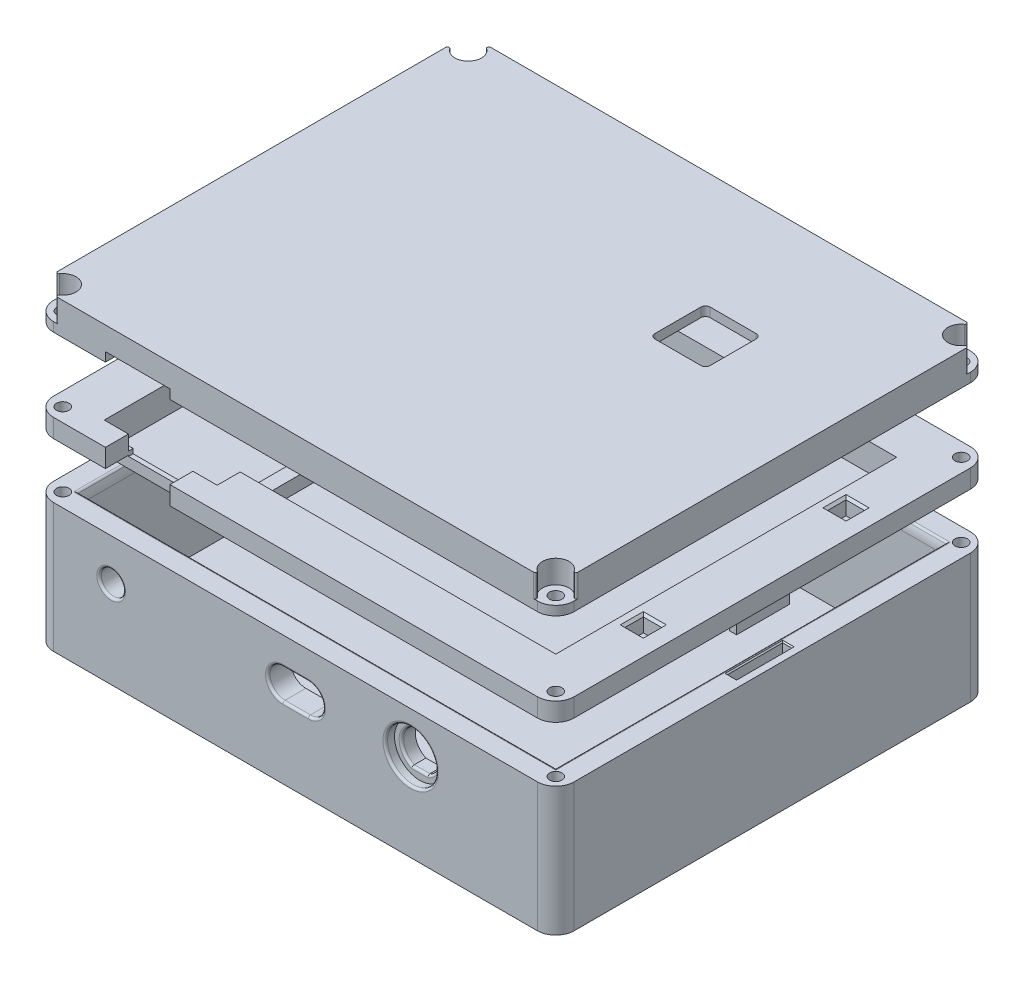
SolidWorks part; units mm, degrees
ref_plane "Front Plane" through (0, 0, 0) normal (0, 0, 1) x (1, 0, 0)
ref_plane "Top Plane" through (0, 0, 0) normal (0, 1, 0) x (1, 0, 0)
ref_plane "Right Plane" through (0, 0, 0) normal (1, 0, 0) x (0, 0, -1)
sketch "Sketch1" plane through (0, 0, 0) normal (0, 1, 0) x (1, 0, 0)
  line L0 (-1, 89) -> (104, 89)
  line L1 (0, 0) -> (103, 0)
  line L2 (0, 0) -> (0, 84)
  line L3 (0, 84) -> (103, 84)
  line L4 (103, 0) -> (103, 84)
  line L5 (108, -1) -> (108, 85)
  line L6 (-1, -5) -> (104, -5)
  line L7 (-5, -1) -> (-5, 85)
  line L8 (0, 0) -> (0, 13.5) construction
  line L9 (0, 84) -> (0, 72) construction
  line L10 (0, 0) -> (4, 0) construction
  line L11 (-5, 89) -> (108, 89) construction
  line L12 (108, -5) -> (108, 89) construction
  line L13 (-5, -5) -> (108, -5) construction
  line L14 (-5, -5) -> (-5, 89) construction
  line L15 (0, 13.5) -> (1.5, 13.5)
  line L20 (1.5, 13.5) -> (1.5, 0)
  line L21 (0, 72) -> (1.5, 72)
  line L22 (1.5, 72) -> (1.5, 84)
  line L23 (4, 0) -> (4, 1.5)
  line L24 (4, 1.5) -> (1.5, 1.5)
  arc A0 (104, 89) -> (108, 85) centre (104, 85) cw
  arc A1 (108, -1) -> (104, -5) centre (104, -1) cw
  arc A2 (-5, -1) -> (-1, -5) centre (-1, -1) ccw
  arc A3 (-5, 85) -> (-1, 89) centre (-1, 85) cw
  dimension "D7" = 4
  dimension "D1" = 103
  dimension "D2" = 84
  dimension "D4" = 13.5
  dimension "D5" = 12
  dimension "D6" = 4
  dimension "D8" = 1.5
  dimension "D9" = 1.5
  dimension "D10" = 1.5
  dimension "D3" = 5
extrude "Boss-Extrude1" add sketch "Sketch1" along normal blind 4 contours L0 A0 L5 A1 L6 A2 L7 A3
extrude "Boss-Extrude2" add sketch "Sketch1<3>" along normal blind 24 from surface contours A3 L7 A2 L6 A1 L5 A0 L0 L4 L1 L2 L3 region at (51.5, 0, -87.5301) starting at face at (51.5, 4, -42)
sketch "Sketch1<3>" plane through (0, 0, 0) normal (0, 1, 0) x (1, 0, 0) same geometry as "Sketch1"
extrude "Boss-Extrude3" add sketch "Sketch1<4>" along normal blind 8 from surface contours L21 L22 L3 L2 | L20 L15 L2 L1 | L23 L24 L20 L1 region at (0.75, 0, -6.75) region at (2.75, 0, -0.75) region at (0.75, 0, -78) starting at face at (51.5, 4, -42)
sketch "Sketch1<4>" plane through (0, 0, 0) normal (0, 1, 0) x (1, 0, 0) same geometry as "Sketch1"
chamfer "Chamfer1" distance 1 angle 45 6 edges at (0.75, 12, -13.5) (4, 12, -0.75) (2.75, 12, -1.5) (1.5, 12, -7.5) (0.75, 12, -72) (1.5, 12, -78)
sketch "Sketch2" plane through (0, 0, 0) normal (0, 0, 1) x (1, 0, 0)
  line L0 (51.5, 0) -> (51.5, 53.6645) construction
  line L1 (108, 0) -> (104, 0) construction
  line L2 (-1, 0) -> (104, 0) construction
  line L3 (-1, 0) -> (-5, 0) construction
  line L4 (108, 0) -> (104, 0) construction
  line L5 (-1, 0) -> (104, 0) construction
  line L6 (-1, 0) -> (-5, 0) construction
  line L7 (4, 4) -> (103, 4) construction
  line L8 (4, 4) -> (103, 4) construction
  line L9 (48.75, 18.7) -> (54.25, 18.7) construction
  line L10 (48.75, 21.95) -> (54.25, 21.95)
  line L11 (48.75, 15.45) -> (54.25, 15.45)
  line L12 (76.5, 4) -> (76.5, 15) construction
  line L13 (76.5, 22.625) -> (76.5, 15.375) construction
  line L14 (74.809, 22.625) -> (78.191, 22.625)
  line L15 (74.809, 15.375) -> (78.191, 15.375)
  arc A0 (48.75, 21.95) -> (48.75, 15.45) centre (48.75, 18.7) ccw
  arc A1 (54.25, 15.45) -> (54.25, 21.95) centre (54.25, 18.7) ccw
  arc A2 (74.809, 22.625) -> (74.809, 15.375) centre (76.5, 19) ccw
  circle A3 centre (76.5, 19) radius 5.5
  arc A4 (78.191, 22.625) -> (74.809, 22.625) centre (76.5, 19) ccw construction
  arc A5 (74.809, 15.375) -> (76.5, 15) centre (76.5, 19) ccw construction
  arc A6 (78.191, 15.375) -> (78.191, 22.625) centre (76.5, 19) ccw
  arc A7 (76.5, 15) -> (78.191, 15.375) centre (76.5, 19) ccw construction
  circle A8 centre (11.5, 19) radius 2.625
  point P6 (51.5, 18.7)
  point P15 (45.5, 18.7)
  point P16 (57.5, 18.7)
  point P26 (76.5, 19)
  point P28 (76.5, 22.625)
  point P31 (76.5, 15.375)
  dimension "D5" = 8
  dimension "D6" = 11
  dimension "D3" = 5.25
  dimension "D1" = 12
  dimension "D2" = 6.5
  dimension "D4" = 11
  dimension "D7" = 25
  dimension "D8" = 7.25
  dimension "D9" = 14.7
  dimension "D10" = 40
  dimension "D11" = 15
extrude "Cut-Extrude1" cut sketch "Sketch2" along normal blind 11 contours L11 A1 L10 A0 | L15 A6 L14 A2 | A8 region at (51.5, 18.7, 0) region at (76.5, 19, 0) region at (11.5, 19, 0)
extrude "Cut-Extrude2" cut sketch "Sketch2<3>" against normal blind 2 from surface contours A3 starting at face at (8.875, 19, 5)
sketch "Sketch2<3>" plane through (0, 0, 0) normal (0, 0, 1) x (1, 0, 0) same geometry as "Sketch2"
chamfer "Chamfer2" distance 0.5 angle 45 4 edges at (103, 28, -42) (51.5, 28, 0) (0, 28, -42) (51.5, 28, -84)
fillet "Fillet1" radius 5 4 edges at (51.5, 27.5, 0) (103, 27.5, -42) (51.5, 27.5, -84) (0, 27.5, -42)
fillet "Fillet2" radius 0.5 10 edges at (51.5, 21.95, 5) (57.5, 18.7, 5) (51.5, 15.45, 5) (71, 19, 5) (80.5, 19, 3) (76.5, 22.625, 3) (76.5, 15.375, 3) (72.5, 19, 3) (45.5, 18.7, 5) (8.875, 19, 5)
sketch "Sketch3" plane through (0, 28, 0) normal (0, 1, 0) x (1, 0, 0)
  line L0 (103, 0) -> (103, 84) construction
  line L1 (0, 0) -> (103, 0) construction
  line L2 (0, 0) -> (0, 84) construction
  line L3 (0, 84) -> (103, 84) construction
  line L4 (103, 0) -> (103, 84) construction
  line L5 (0, 0) -> (103, 0) construction
  line L6 (0, 0) -> (0, 84) construction
  line L7 (0, 84) -> (103, 84) construction
  line L8 (105, -2) -> (105, 86) construction
  line L9 (-2, 86) -> (105, 86) construction
  line L10 (-2, -2) -> (-2, 86) construction
  line L11 (-2, -2) -> (105, -2) construction
  line L12 (51.5, 86) -> (51.5, -2) construction
  line L13 (-1.25, 48) -> (-3.25, 48)
  line L14 (-1.25, 48) -> (-1.25, 36)
  line L15 (-1.25, 36) -> (-3.25, 36)
  line L16 (-3.25, 48) -> (-3.25, 36)
  line L17 (-1.25, 48) -> (-3.25, 36) construction
  line L18 (-1.25, 36) -> (-3.25, 48) construction
  line L19 (104.25, 36) -> (106.25, 36)
  line L20 (106.25, 48) -> (106.25, 36)
  line L21 (104.25, 48) -> (106.25, 48)
  line L22 (104.25, 48) -> (104.25, 36)
  circle A0 centre (-2, 86) radius 1.35
  circle A1 centre (105, 86) radius 1.35
  circle A2 centre (105, -2) radius 1.35
  circle A3 centre (-2, -2) radius 1.35
  point P12 (-2.25, 42)
  point P25 (-2, 42)
  dimension "D2" = 2.7
  dimension "D3" = 2.7
  dimension "D4" = 2.7
  dimension "D5" = 2.7
  dimension "D6" = 2
  dimension "D7" = 12
  dimension "D8" = 0.25
  dimension "D1" = 2
extrude "Cut-Extrude3" cut sketch "Sketch3" against normal blind 8 contours A3 | A2 | A1 | A0 region at (-2, 28, -86) region at (105, 28, -86) region at (105, 28, 2) region at (-2, 28, 2)
extrude "Cut-Extrude12" cut sketch "Sketch3<3>" against normal blind 4 contours L15 L16 L13 L14 | L19 L20 L21 L22
sketch "Sketch3<3>" plane through (0, 28, 0) normal (0, 1, 0) x (1, 0, 0) same geometry as "Sketch3"
ref_plane "Plane1" through (0, 40, 0) normal (0, 1, 0) x (1, 0, 0)
sketch "Sketch4" plane through (0, 40, 0) normal (0, 1, 0) x (1, 0, 0)
  line L4 (0, 0) -> (103, 0)
  line L5 (103, 0) -> (103, 84)
  line L6 (103, 84) -> (0, 84)
  line L7 (0, 84) -> (0, 0)
  line L8 (0, 0) -> (103, 0)
  line L9 (103, 0) -> (103, 84)
  line L10 (103, 84) -> (0, 84)
  line L11 (0, 84) -> (0, 0)
  line L12 (104, 89) -> (-1, 89)
  line L13 (108, -1) -> (108, 85)
  line L14 (-1, -5) -> (104, -5)
  line L15 (-5, 85) -> (-5, -1)
  line L16 (104, 89) -> (-1, 89)
  line L17 (108, -1) -> (108, 85)
  line L18 (-1, -5) -> (104, -5)
  line L19 (-5, 85) -> (-5, -1)
  line L23 (98, 79) -> (5, 79)
  line L25 (5, 79) -> (5, 5)
  line L26 (5, 5) -> (98, 5)
  line L28 (98, 5) -> (98, 79)
  line L29 (104.25, 36) -> (106.25, 36)
  line L30 (106.25, 36) -> (106.25, 48)
  line L31 (106.25, 48) -> (104.25, 48)
  line L32 (104.25, 48) -> (104.25, 36)
  line L33 (104.25, 36) -> (106.25, 36)
  line L34 (106.25, 36) -> (106.25, 48)
  line L35 (106.25, 48) -> (104.25, 48)
  line L36 (104.25, 48) -> (104.25, 36)
  line L37 (-1.25, 48) -> (-3.25, 48)
  line L38 (-1.25, 36) -> (-1.25, 48)
  line L39 (-3.25, 36) -> (-1.25, 36)
  line L40 (-3.25, 48) -> (-3.25, 36)
  line L41 (-1.25, 48) -> (-3.25, 48)
  line L42 (-1.25, 36) -> (-1.25, 48)
  line L43 (-3.25, 36) -> (-1.25, 36)
  line L44 (-3.25, 48) -> (-3.25, 36)
  line L45 (-1.5, 47.75) -> (-3, 47.75)
  line L46 (-3, 47.75) -> (-3, 36.25)
  line L47 (-3, 36.25) -> (-1.5, 36.25)
  line L48 (-1.5, 36.25) -> (-1.5, 47.75)
  line L49 (104.5, 36.25) -> (106, 36.25)
  line L50 (106, 36.25) -> (106, 47.75)
  line L51 (106, 47.75) -> (104.5, 47.75)
  line L52 (104.5, 47.75) -> (104.5, 36.25)
  line L53 (5, 5) -> (5, 0)
  line L54 (29.5, 5) -> (29.5, 0)
  circle A1 centre (-2, -2) radius 1.35
  circle A2 centre (-2, -2) radius 1.35
  circle A3 centre (105, -2) radius 1.35
  arc A4 (108, 85) -> (104, 89) centre (104, 85) ccw
  arc A5 (104, -5) -> (108, -1) centre (104, -1) ccw
  arc A6 (-5, -1) -> (-1, -5) centre (-1, -1) ccw
  arc A7 (-1, 89) -> (-5, 85) centre (-1, 85) ccw
  arc A8 (108, 85) -> (104, 89) centre (104, 85) ccw
  arc A9 (104, -5) -> (108, -1) centre (104, -1) ccw
  arc A10 (-5, -1) -> (-1, -5) centre (-1, -1) ccw
  arc A11 (-1, 89) -> (-5, 85) centre (-1, 85) ccw
  circle A12 centre (105, -2) radius 1.35
  circle A13 centre (105, 86) radius 1.35
  circle A14 centre (105, 86) radius 1.35
  circle A15 centre (-2, 86) radius 1.35
  circle A16 centre (-2, 86) radius 1.35
  dimension "D11" = 24.5
  dimension "D1" = 0
  dimension "D2" = 0
  dimension "D3" = 0
  dimension "D4" = 0
  dimension "D5" = 0
  dimension "D6" = 0
  dimension "D7" = 0
  dimension "D8" = 0
  dimension "D9" = 5
  dimension "D10" = 0.25
extrude "Boss-Extrude4" add sketch "Sketch4" along normal blind 4 separate body contours L16 A11 L19 A10 L18 A9 L17 A8 A16 A14 A12 L11 L10 L9 L8 L36 L35 L34 L33 L44 L41 L42 L43 A2 | L41 L44 L43 L42 | L35 L36 L33 L34 region at (106.7245, 40, -87.7245)
extrude "Boss-Extrude7" add sketch "Sketch4<5>" against normal blind 4 contours L46 L47 L48 L45 | L50 L51 L52 L49
sketch "Sketch4<5>" plane through (0, 40, 0) normal (0, 1, 0) x (1, 0, 0) same geometry as "Sketch4"
extrude "Boss-Extrude5" add sketch "Sketch4<3>" along normal mid plane 8 contours L10 L11 L8 L9 L28 L26 L25 L23 region at (1.3291, 40, -42)
sketch "Sketch4<3>" plane through (0, 40, 0) normal (0, 1, 0) x (1, 0, 0) same geometry as "Sketch4"
extrude "Boss-Extrude6" add sketch "Sketch4<4>" along normal blind 2 from surface contours L23 L25 L26 L28 starting at face at (47.1, 36, -33.6)
sketch "Sketch4<4>" plane through (0, 40, 0) normal (0, 1, 0) x (1, 0, 0) same geometry as "Sketch4"
sketch "Sketch5" plane through (0, 0, -5) normal (0, 0, 1) x (1, 0, 0)
  line L4 (5, 36) -> (29.5, 36)
  line L5 (29.5, 36) -> (29.5, 38)
  line L6 (29.5, 38) -> (5, 38)
  line L7 (5, 38) -> (5, 36)
  line L8 (5, 36) -> (29.5, 36)
  line L9 (29.5, 36) -> (29.5, 38)
  line L10 (29.5, 38) -> (5, 38)
  line L11 (5, 38) -> (5, 36)
  dimension "D1" = 0
extrude "Boss-Extrude8" add sketch "Sketch5" along normal up to surface (5 mm away) up to face at (2.5, 38, 0)
chamfer "Chamfer3" distance 1.5 angle 45 4 edges at (103, 36, -42) (51.5, 36, -84) (51.5, 36, 0) (0, 36, -42)
sketch "Sketch7" plane through (0, 0, 0) normal (0, 0, 1) x (1, 0, 0)
  line L0 (29.5, 40) -> (29.5, 38) construction
  line L2 (5, 40) -> (5, 38) construction
  line L3 (29.5, 40.7937) -> (29.5, 37.7398)
  line L4 (5, 37.7398) -> (29.5, 37.7398)
  line L5 (5, 40.7937) -> (5, 37.7398)
  line L6 (5, 40.7937) -> (29.5, 40.7937)
extrude "Boss-Extrude11" add sketch "Sketch7" against normal blind 1
sketch "Sketch6" plane through (0, 0, 0) normal (0, 0, 1) x (1, 0, 0)
  line L0 (5, 38) -> (29.5, 38) construction
  line L1 (5, 38) -> (29.5, 38) construction
  line L2 (17.25, 38) -> (17.25, 44.8184) construction
  line L3 (10.25, 39.8) -> (24.25, 39.8)
  line L4 (10.25, 41.5) -> (24.25, 41.5)
  line L5 (0, 37.5) -> (103, 37.5) construction
  line L6 (10.25, 41.5) -> (10.25, 39.8)
  line L7 (24.25, 41.5) -> (24.25, 39.8)
  line L8 (10.25, 41.5) -> (10.25, 44.8184)
  line L9 (10.25, 44.8184) -> (24.25, 44.8184)
  line L10 (24.25, 44.8184) -> (24.25, 41.5)
  point P7 (17.25, 39.8)
  point P10 (17.25, 41.5)
  dimension "D1" = 14
  dimension "D2" = 1.8
  dimension "D3" = 14
  dimension "D4" = 4
extrude "Cut-Extrude4" cut sketch "Sketch6" along normal mid plane 15 contours L10 L9 L8 L4 | L7 L3 L6 L4 region at (17.25, 43.1592, 0)
sketch "Sketch8" plane through (0, 38, 0) normal (0, 1, 0) x (1, 0, 0)
  line L0 (5, 44) -> (29.5, 44)
  line L1 (5, 79) -> (5, 1) construction
  line L2 (29.5, 1) -> (5, 1) construction
  line L3 (29.5, 44) -> (29.5, 5)
  line L4 (5, 48) -> (33.5, 48)
  line L5 (33.5, 48) -> (33.5, 5)
  line L7 (9.25, 52) -> (25.25, 52)
  line L8 (9.25, 52) -> (9.25, 56)
  line L9 (9.25, 56) -> (25.25, 56)
  line L10 (25.25, 52) -> (25.25, 56)
  point P16 (17.25, 52)
  point P17 (17.25, 44)
  line M11 (29.5, 5) -> (98, 5)
  line M14 (5, 79) -> (5, 1)
  dimension "D1" = 43
  dimension "D2" = 24.5
  dimension "D3" = 4
  dimension "D4" = 4
  dimension "D5" = 4
  dimension "D6" = 16
  dimension "D7" = 4
extrude "Boss-Extrude12" add sketch "Sketch8" along normal blind 3 contours L5 L4 L0 L3 M14 M11 region at (5.5159, 38, -46)
extrude "Cut-Extrude5" cut sketch "Sketch8<3>" against normal blind 3.5 contours L9 L10 L7 L8
sketch "Sketch8<3>" plane through (0, 38, 0) normal (0, 1, 0) x (1, 0, 0) same geometry as "Sketch8"
chamfer "Chamfer4" distance 1 angle 45 6 edges at (25.25, 38, -54) (17.25, 38, -56) (9.25, 38, -54) (17.25, 38, -52) (29.5, 41, -24.5) (17.25, 41, -44)
sketch "Sketch10" plane through (0, 38, 0) normal (0, 1, 0) x (1, 0, 0)
  line L0 (77.5, 64) -> (77.5, 52) construction
  line L1 (73.5, 64) -> (81.5, 64)
  line L2 (71.5, 62) -> (71.5, 54)
  line L3 (73.5, 52) -> (81.5, 52)
  line L4 (83.5, 62) -> (83.5, 54)
  line L5 (73.7129, 58) -> (81.5, 58) construction
  line L6 (82.5, 61.375) -> (84.5, 61.375)
  line L7 (82.5, 61.375) -> (82.5, 59.625)
  line L8 (82.5, 59.625) -> (84.5, 59.625)
  line L9 (84.5, 61.375) -> (84.5, 59.625)
  line L10 (82.5, 61.375) -> (84.5, 59.625) construction
  line L11 (82.5, 59.625) -> (84.5, 61.375) construction
  line L12 (82.5, 56.375) -> (84.5, 56.375)
  line L13 (84.5, 54.625) -> (84.5, 56.375)
  line L14 (82.5, 54.625) -> (84.5, 54.625)
  line L15 (82.5, 54.625) -> (82.5, 56.375)
  line L16 (72.5, 59.625) -> (70.5, 59.625)
  line L17 (70.5, 61.375) -> (70.5, 59.625)
  line L18 (72.5, 61.375) -> (70.5, 61.375)
  line L19 (72.5, 61.375) -> (72.5, 59.625)
  line L20 (72.5, 54.625) -> (72.5, 56.375)
  line L21 (72.5, 54.625) -> (70.5, 54.625)
  line L22 (70.5, 54.625) -> (70.5, 56.375)
  line L23 (72.5, 56.375) -> (70.5, 56.375)
  line L24 (51.5, 89) -> (51.5, -5) construction
  line L25 (-1, 89) -> (104, 89) construction
  line L26 (-1, -5) -> (104, -5) construction
  line L27 (-5, 42) -> (108, 42) construction
  line L28 (-5, -1) -> (-5, 85) construction
  line L29 (108, -1) -> (108, 85) construction
  line L30 (3, 18) -> (3, 22)
  line L31 (-1, 66) -> (3, 66)
  line L32 (-1, 66) -> (-1, 62)
  line L33 (-1, 62) -> (3, 62)
  line L34 (3, 66) -> (3, 62)
  line L35 (-1, 22) -> (3, 22)
  line L36 (-1, 18) -> (-1, 22)
  line L37 (-1, 18) -> (3, 18)
  line L39 (100, 18) -> (100, 22)
  line L40 (104, 18) -> (100, 18)
  line L41 (104, 18) -> (104, 22)
  line L42 (104, 22) -> (100, 22)
  line L43 (104, 62) -> (100, 62)
  line L44 (100, 66) -> (100, 62)
  line L45 (104, 66) -> (104, 62)
  line L46 (104, 66) -> (100, 66)
  circle A0 centre (77.5, 62.35) radius 0.8
  circle A1 centre (77.5, 53.65) radius 0.8
  arc A2 (71.5, 54) -> (73.5, 52) centre (73.5, 54) ccw
  arc A3 (81.5, 52) -> (83.5, 54) centre (81.5, 54) ccw
  arc A4 (83.5, 62) -> (81.5, 64) centre (81.5, 62) ccw
  arc A5 (71.5, 62) -> (73.5, 64) centre (73.5, 62) cw
  point P10 (77.5, 58)
  point P13 (71.5, 52)
  point P16 (83.5, 52)
  point P21 (71.5, 64)
  point P22 (83.5, 60.5)
  dimension "D3" = 1.6
  dimension "D4" = 1.6
  dimension "D7" = 2
  dimension "D1" = 12
  dimension "D2" = 12
  dimension "D5" = 8.7
  dimension "D6" = 4.35
  dimension "D8" = 1.75
  dimension "D9" = 2
  dimension "D10" = 2.5
  dimension "D11" = 4
  dimension "D12" = 4
  dimension "D13" = 20
  dimension "D14" = 48.5
  dimension "D15" = 20
  dimension "D16" = 10
extrude "Cut-Extrude6" cut sketch "Sketch10" against normal blind 3.5 from surface contours L36 L37 L30 L35 | L41 L42 L39 L40 | L45 L46 L44 L43 | L34 L31 L32 L33 region at (1, 38, -20) region at (1, 38, -64) region at (102, 38, -20) region at (102, 38, -64) starting at face at (41.4444, 44, -27.4444)
extrude "Boss-Extrude13" add sketch "Sketch10<3>" along normal blind 1.5 contours A5 L2 L18 L19 L16 L23 L20 L21 A2 L3 A3 L4 L14 L15 L12 L8 L7 L6 A4 L1 A1 A0 region at (77.5, 38, -58)
sketch "Sketch10<3>" plane through (0, 38, 0) normal (0, 1, 0) x (1, 0, 0) same geometry as "Sketch10"
extrude "Cut-Extrude7" cut sketch "Sketch10<4>" against normal up to next (2 mm away) contours L9 L6 L4 L8 | L7 L8 L4 L6 | L4 L14 L13 L12 | L15 L14 L4 L12 | L20 L23 L2 L21 | L2 L23 L22 L21 | L19 L18 L2 L16 | L17 L16 L19 L18 region at (72, 38, -60.5) region at (84, 38, -60.5) region at (83, 38, -60.5) region at (72, 38, -55.5) region at (71, 38, -55.5) region at (84, 38, -55.5) region at (83, 38, -55.5)
sketch "Sketch10<4>" plane through (0, 38, 0) normal (0, 1, 0) x (1, 0, 0) same geometry as "Sketch10"
fillet "Fillet3" radius 0.5 2 edges at (77.5, 39.5, -52.85) (77.5, 39.5, -61.55)
chamfer "Chamfer5" distance 0.5 angle 45 16 edges at (104, 44, -64) (102, 44, -62) (100, 44, -64) (102, 44, -66) (104, 44, -20) (102, 44, -18) (100, 44, -20) (102, 44, -22) (3, 44, -20) (1, 44, -18) (-1, 44, -20) (1, 44, -22) (1, 44, -62) (3, 44, -64) (-1, 44, -64) (1, 44, -66)
ref_plane "Plane3" through (0, 60, 0) normal (0, 1, 0) x (1, 0, 0)
sketch "Sketch12" plane through (0, 60, 0) normal (0, 1, 0) x (1, 0, 0)
  line L0 (29.5, 5) -> (5, 5)
  line L1 (24.25, -5) -> (10.25, -5)
  line L2 (100, 66) -> (100, 62) construction
  line L7 (72.5, 64) -> (82.5, 64)
  line L8 (71.5, 63) -> (71.5, 53)
  line L9 (72.5, 52) -> (82.5, 52)
  line L10 (83.5, 63) -> (83.5, 53)
  line L11 (71.5, 64) -> (83.5, 52) construction
  line L12 (71.5, 52) -> (83.5, 64) construction
  line L13 (100, 62) -> (104, 62) construction
  line L14 (24.25, 0) -> (24.25, -5)
  line L15 (24.25, -5) -> (104, -5)
  line L16 (108, -1) -> (108, 85)
  line L17 (104, 89) -> (-1, 89)
  line L18 (-5, 85) -> (-5, -1)
  line L19 (-1, -5) -> (10.25, -5)
  line L20 (10.25, -5) -> (10.25, 0)
  line L21 (10.25, 0) -> (5, 0)
  line L22 (5, 0) -> (5, 79)
  line L23 (5, 79) -> (98, 79)
  line L24 (98, 79) -> (98, 5)
  line L25 (98, 5) -> (29.5, 5)
  line L26 (29.5, 5) -> (29.5, 0)
  line L27 (29.5, 0) -> (24.25, 0)
  line L28 (24.25, 0) -> (24.25, -5)
  line L29 (24.25, -5) -> (104, -5)
  line L30 (108, -1) -> (108, 85)
  line L31 (104, 89) -> (-1, 89)
  line L32 (-5, 85) -> (-5, -1)
  line L33 (-1, -5) -> (10.25, -5)
  line L34 (10.25, -5) -> (10.25, 0)
  line L35 (10.25, 0) -> (5, 0)
  line L36 (5, 0) -> (5, 79)
  line L37 (5, 79) -> (98, 79)
  line L38 (98, 79) -> (98, 5)
  line L39 (98, 5) -> (29.5, 5)
  line L40 (29.5, 5) -> (29.5, 0)
  line L41 (29.5, 0) -> (24.25, 0)
  line L42 (104, 62) -> (104, 66) construction
  line L43 (104, 66) -> (100, 66) construction
  line L44 (100, 18) -> (104, 18) construction
  line L45 (104, 18) -> (104, 22) construction
  line L46 (104, 22) -> (100, 22) construction
  line L47 (100, 22) -> (100, 18) construction
  line L48 (3, 18) -> (3, 22) construction
  line L49 (3, 22) -> (-1, 22) construction
  line L62 (-1, 22) -> (-1, 18) construction
  line L63 (-1, 18) -> (3, 18) construction
  line L64 (-1, 62) -> (3, 62) construction
  line L65 (3, 62) -> (3, 66) construction
  line L66 (3, 66) -> (-1, 66) construction
  line L67 (-1, 66) -> (-1, 62) construction
  line L68 (100, 66) -> (100, 62) construction
  line L69 (100, 62) -> (104, 62) construction
  line L70 (104, 62) -> (104, 66) construction
  line L71 (104, 66) -> (100, 66) construction
  line L72 (100, 18) -> (104, 18) construction
  line L73 (104, 18) -> (104, 22) construction
  line L74 (104, 22) -> (100, 22) construction
  line L75 (100, 22) -> (100, 18) construction
  line L76 (3, 18) -> (3, 22) construction
  line L77 (3, 22) -> (-1, 22) construction
  line L78 (-1, 22) -> (-1, 18) construction
  line L79 (-1, 18) -> (3, 18) construction
  line L80 (-1, 62) -> (3, 62) construction
  line L81 (3, 62) -> (3, 66) construction
  line L82 (3, 66) -> (-1, 66) construction
  line L83 (-1, 66) -> (-1, 62) construction
  line L84 (-0.65, 62.35) -> (2.65, 62.35)
  line L85 (2.65, 62.35) -> (2.65, 65.65)
  line L86 (2.65, 65.65) -> (-0.65, 65.65)
  line L87 (-0.65, 65.65) -> (-0.65, 62.35)
  line L88 (2.65, 18.35) -> (2.65, 21.65)
  line L89 (2.65, 21.65) -> (-0.65, 21.65)
  line L90 (-0.65, 21.65) -> (-0.65, 18.35)
  line L91 (-0.65, 18.35) -> (2.65, 18.35)
  line L92 (100.35, 18.35) -> (103.65, 18.35)
  line L93 (103.65, 18.35) -> (103.65, 21.65)
  line L94 (103.65, 21.65) -> (100.35, 21.65)
  line L95 (100.35, 21.65) -> (100.35, 18.35)
  line L96 (100.35, 65.65) -> (100.35, 62.35)
  line L97 (100.35, 62.35) -> (103.65, 62.35)
  line L98 (103.65, 62.35) -> (103.65, 65.65)
  line L99 (103.65, 65.65) -> (100.35, 65.65)
  arc A0 (83.5, 63) -> (82.5, 64) centre (82.5, 63) ccw
  arc A1 (83.5, 53) -> (82.5, 52) centre (82.5, 53) cw
  arc A2 (71.5, 53) -> (72.5, 52) centre (72.5, 53) ccw
  arc A3 (71.5, 63) -> (72.5, 64) centre (72.5, 63) cw
  arc A4 (104, -5) -> (108, -1) centre (104, -1) ccw
  arc A5 (108, 85) -> (104, 89) centre (104, 85) ccw
  arc A6 (-1, 89) -> (-5, 85) centre (-1, 85) ccw
  arc A7 (-5, -1) -> (-1, -5) centre (-1, -1) ccw
  arc A8 (104, -5) -> (108, -1) centre (104, -1) ccw
  arc A9 (108, 85) -> (104, 89) centre (104, 85) ccw
  arc A10 (-1, 89) -> (-5, 85) centre (-1, 85) ccw
  arc A11 (-5, -1) -> (-1, -5) centre (-1, -1) ccw
  point P4 (77.5, 58)
  dimension "D3" = 1
  dimension "D2" = 12
  dimension "D1" = 0
  dimension "D4" = 0.35
extrude "Boss-Extrude14" add sketch "Sketch12" along normal blind 5 separate body contours L32 A11 L33 L34 L35 L36 L37 L38 L39 L40 L41 L28 L29 A8 L30 A9 L31 A10 | L41 L40 L0 L36 L35 L34 L1 L28 | L86 L87 L84 L85 | L90 L91 L88 L89 | L94 L95 L92 L93 | L98 L99 L96 L97 region at (17.25, 60, -0.6818) region at (63.75, 60, -3.5301) region at (1, 60, -64) region at (1, 60, -20) region at (102, 60, -20) region at (102, 60, -64)
sketch "Sketch13" plane through (0, 0, 5) normal (0, 0, 1) x (1, 0, 0)
  line L0 (10.25, 60) -> (24.25, 60)
  line L1 (24.25, 60) -> (24.25, 62)
  line L2 (24.25, 62) -> (10.25, 62)
  line L3 (10.25, 62) -> (10.25, 60)
  dimension "D1" = 2
extrude "Cut-Extrude8" cut sketch "Sketch13" against normal up to next (10 mm away)
extrude "Boss-Extrude15" add sketch "Sketch12<3>" along normal blind 2 from surface contours L39 L38 L37 L36 L0 L8 A3 L7 A0 L10 A1 L9 A2 | L32 A11 L33 L34 L35 L36 L37 L38 L39 L40 L41 L28 L29 A8 L30 A9 L31 A10 L87 L86 L85 L84 L91 L90 L89 L88 L95 L94 L93 L92 L99 L98 L97 L96 | L41 L40 L0 L36 L35 L34 L1 L28 | L90 L91 L88 L89 | L86 L87 L84 L85 | L98 L99 L96 L97 | L94 L95 L92 L93 region at (17.25, 60, -0.6818) region at (50.9477, 60, -41.6601) region at (63.75, 60, -3.5301) region at (1, 60, -64) region at (1, 60, -20) region at (102, 60, -20) region at (102, 60, -64) starting at face at (51.5, 65, -42)
sketch "Sketch12<3>" plane through (0, 60, 0) normal (0, 1, 0) x (1, 0, 0) same geometry as "Sketch12"
sketch "Sketch14" plane through (0, 60, 0) normal (0, 1, 0) x (1, 0, 0)
  circle A0 centre (-2, 86) radius 1.35 construction
  circle A1 centre (105, 86) radius 1.35 construction
  circle A2 centre (105, -2) radius 1.35 construction
  circle A3 centre (-2, -2) radius 1.35 construction
  circle A4 centre (-2, 86) radius 1.35
  circle A5 centre (105, 86) radius 1.35
  circle A6 centre (105, -2) radius 1.35
  circle A7 centre (-2, -2) radius 1.35
  circle A8 centre (-2, -2) radius 2.875
  circle A9 centre (-2, 86) radius 2.875
  circle A10 centre (105, 86) radius 2.875
  circle A11 centre (105, -2) radius 2.875
  dimension "D1" = 5.75
  dimension "D2" = 5.75
  dimension "D3" = 5.75
  dimension "D4" = 5.75
extrude "Cut-Extrude9" cut sketch "Sketch14" along normal up to next (7 mm away) contours A4 | A5 | A6 | A7
extrude "Cut-Extrude10" cut sketch "Sketch14<3>" along normal blind 5 from offset 2 contours A9 | A10 | A8 | A11
sketch "Sketch14<3>" plane through (0, 60, 0) normal (0, 1, 0) x (1, 0, 0) same geometry as "Sketch14"
fillet "Fillet4" radius 0.35 8 edges at (-1.9922, 64.5, -88.875) (-4.875, 64.5, -85.9922) (107.875, 64.5, -85.9922) (104.9922, 64.5, -88.875) (104.9922, 64.5, 4.875) (107.875, 64.5, 1.9922) (-1.9922, 64.5, 4.875) (-4.875, 64.5, 1.9922)
sketch "Sketch17" plane through (0, 0, -89) normal (0, 0, -1) x (-1, 0, 0)
  line L0 (-1.5, 4) -> (-103, 4) construction
  line L1 (-1.5, 4) -> (-103, 4) construction
  line L2 (-52.25, 4) -> (-52.25, 34.8114) construction
  line L3 (-68.25, 24) -> (-68.25, 14) construction
  line L4 (-73.25, 19) -> (-63.25, 19) construction
  circle A0 centre (-68.25, 19) radius 5
  circle A1 centre (-68.25, 19) radius 6
  dimension "D3" = 10
  dimension "D4" = 12
  dimension "D1" = 10
  dimension "D2" = 21
extrude "Cut-Extrude11" cut sketch "Sketch17" against normal blind 5 contours A0 region at (68.25, 19, -89)
chamfer "Chamfer6" distance 0.25 angle 45 8 edges at (106.25, 28, -42) (105.25, 28, -48) (104.25, 28, -42) (105.25, 28, -36) (-2.25, 28, -36) (-1.25, 28, -42) (-2.25, 28, -48) (-3.25, 28, -42)
fillet "Fillet5" radius 1 2 edges at (63.25, 19, -89) (63.25, 19, -84)
fillet "Fillet6" radius 0.5 4 edges at (103.5, 28, -42) (51.5, 28, 0.5) (-0.5, 28, -42) (51.5, 28, -84.5)
sketch "Sketch18" plane through (103, 0, 0) normal (-1, 0, 0) x (0, 0, 1)
  line L0 (-58, 34.8792) -> (-58, 37.0792) construction
  line L1 (-60, 20.9869) -> (-56, 20.9869)
  line L2 (-60, 20.9869) -> (-60, 16.9869)
  line L3 (-60, 16.9869) -> (-56, 16.9869)
  line L4 (-56, 20.9869) -> (-56, 16.9869)
  line L5 (-60, 20.9869) -> (-56, 16.9869) construction
  line L6 (-60, 16.9869) -> (-56, 20.9869) construction
  line L8 (-59.5, 10.9869) -> (-56.5, 10.9869)
  line L9 (-59.5, 10.9869) -> (-59.5, 13.9869)
  line L10 (-59.5, 13.9869) -> (-56.5, 13.9869)
  line L11 (-56.5, 10.9869) -> (-56.5, 13.9869)
  line L12 (-59.5, 10.9869) -> (-56.5, 13.9869) construction
  line L13 (-59.5, 13.9869) -> (-56.5, 10.9869) construction
  point P0 (-58, 18.9869)
  point P9 (-58, 12.4869)
  dimension "D1" = 4
  dimension "D2" = 4
  dimension "D3" = 3
  dimension "D4" = 3
  dimension "D5" = 3
extrude "Cut-Extrude13" cut sketch "Sketch18" against normal blind 3
chamfer "Chamfer7" distance 0.325 angle 45 8 edges at (103, 12.4869, -56.5) (103, 13.9869, -58) (103, 12.4869, -59.5) (103, 10.9869, -58) (103, 18.9869, -56) (103, 20.9869, -58) (103, 16.9869, -58) (103, 18.9869, -60)
